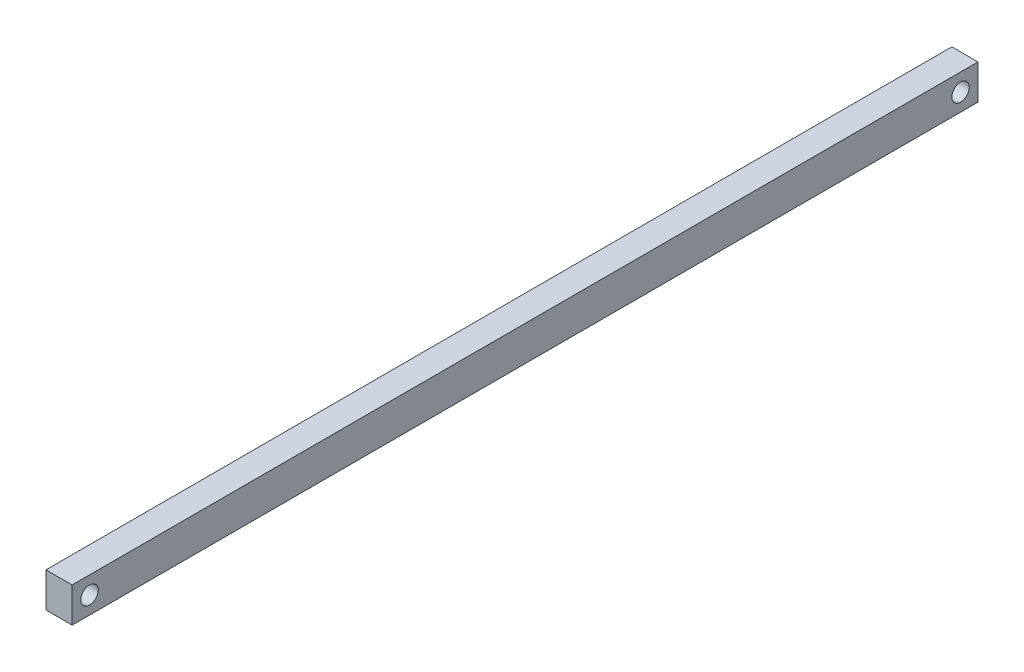
SolidWorks part; units mm, degrees
ref_plane "Front Plane" through (0, 0, 0) normal (0, 0, 1) x (1, 0, 0)
ref_plane "Top Plane" through (0, 0, 0) normal (0, 1, 0) x (1, 0, 0)
ref_plane "Right Plane" through (0, 0, 0) normal (1, 0, 0) x (0, 0, -1)
sketch "Sketch1" plane through (0, 0, 0) normal (0, 0, 1) x (1, 0, 0)
  line L5 (-9.525, -12.7) -> (9.525, -12.7)
  line L6 (-9.525, -12.7) -> (-9.525, 12.7)
  line L7 (-9.525, 12.7) -> (9.525, 12.7)
  line L8 (9.525, -12.7) -> (9.525, 12.7)
  line L9 (-9.525, -12.7) -> (9.525, 12.7) construction
  line L10 (-9.525, 12.7) -> (9.525, -12.7) construction
  point P0 (0, 0)
  dimension "D1" = 25.4
  dimension "D2" = 19.05
extrude "Boss-Extrude1" add sketch "Sketch1" along normal blind 660.4
sketch "Sketch2" plane through (-9.525, 0, 0) normal (1, 0, 0) x (0, 0, -1)
  line L0 (0, 0) -> (-660.4, 0) construction
  line L1 (-660.4, 12.7) -> (-660.4, -12.7) construction
  line L2 (-330.2, 0) -> (-330.2, 46.4779) construction
  line L4 (0, -12.7) -> (0, 12.7) construction
  circle A0 centre (-12.7, 0) radius 6.35
  circle A1 centre (-647.7, 0) radius 6.35
  point P9 (-35.6849, 0)
  dimension "D1" = 12.7
  dimension "D2" = 12.7
extrude "Cut-Extrude4" cut sketch "Sketch2" against normal through all and the other way through all contours A1 | A0
